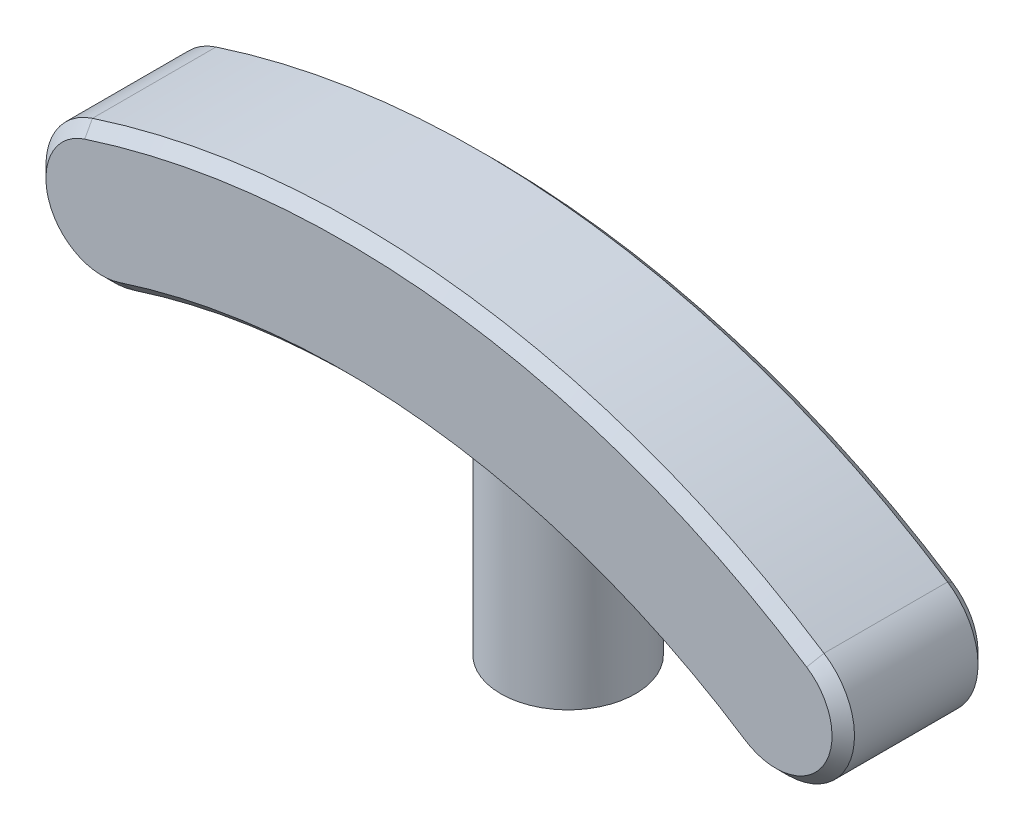
SolidWorks part; units mm, degrees
material "ABS PC"
ref_plane "Front Plane" through (0, 0, 0) normal (0, 0, 1) x (1, 0, 0)
ref_plane "Top Plane" through (0, 0, 0) normal (0, 1, 0) x (1, 0, 0)
ref_plane "Right Plane" through (0, 0, 0) normal (1, 0, 0) x (0, 0, -1)
sketch "Sketch1" plane through (0, 0, 0) normal (0, 1, 0) x (1, 0, 0)
  circle A0 centre (0, 0) radius 6
  dimension "D1" = 12
extrude "Boss-Extrude1" add sketch "Sketch1" along normal blind 24
sketch "Sketch2" plane through (0, 0, 0) normal (0, 0, 1) x (1, 0, 0)
  line L0 (-6, 0) -> (6, 0) construction
  arc A0 (-35, 20) -> (25, 12) centre (-13.342, -46.5652) cw construction
  arc A1 (-33.1436, 14.2944) -> (21.7135, 6.9801) centre (-13.342, -46.5652) cw
  arc A2 (-36.8564, 25.7056) -> (28.2865, 17.0199) centre (-13.342, -46.5652) cw
  arc A3 (-36.8564, 25.7056) -> (-33.1436, 14.2944) centre (-35, 20) ccw
  arc A4 (28.2865, 17.0199) -> (21.7135, 6.9801) centre (25, 12) cw
  dimension "D1" = 70
  dimension "D2" = 25
  dimension "D3" = 12
  dimension "D4" = 20
  dimension "D5" = 35
  dimension "D6" = 6
extrude "Boss-Extrude2" add sketch "Sketch2" along normal mid plane 13
chamfer "Chamfer1" distance 1 angle 45 8 edges at (-4.8836, 16.8733, -6.5) (30.0199, 8.7135, -6.5) (-3.2976, 28.7681, -6.5) (-40.7056, 18.1436, -6.5) (-3.2976, 28.7681, 6.5) (30.0199, 8.7135, 6.5) (-4.8836, 16.8733, 6.5) (-40.7056, 18.1436, 6.5)
fillet "Fillet1" radius 3 2 edges at (5.9983, 14.4425, -0.1427) (-5.8633, 16.9963, -1.2734)
sketch "Sketch3" plane through (0, 0, 0) normal (0, -1, 0) x (1, 0, 0)
  circle A0 centre (0, 0) radius 4
  dimension "D1" = 8
extrude "Cut-Extrude1" cut sketch "Sketch3" against normal blind 10
